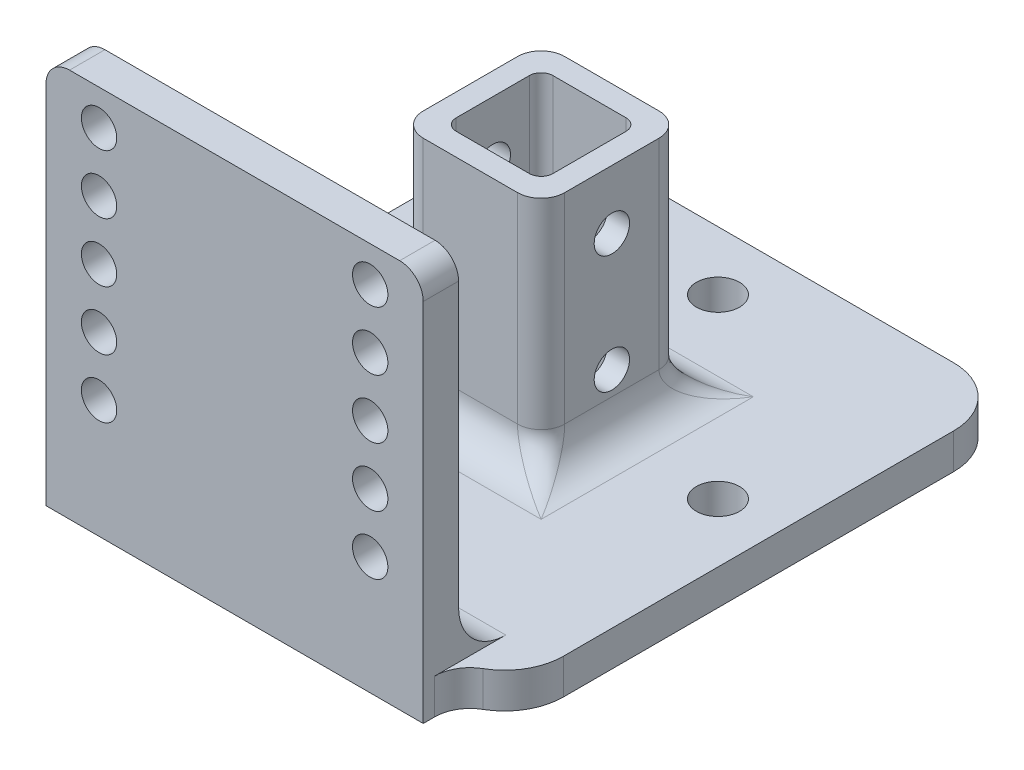
SolidWorks part; units mm, degrees
ref_plane "前视基准面" through (0, 0, 0) normal (0, 0, 1) x (1, 0, 0)
ref_plane "上视基准面" through (0, 0, 0) normal (0, 1, 0) x (1, 0, 0)
ref_plane "右视基准面" through (0, 0, 0) normal (1, 0, 0) x (0, 0, -1)
sketch "草图1" plane through (0, 0, 0) normal (0, 1, 0) x (1, 0, 0)
  line L0 (0, 0) -> (0, 22.885) construction
  line L1 (0, 0) -> (-22.885, 0) construction
  line L3 (-20, -23) -> (20, -23)
  line L4 (-20, -23) -> (-20, 20)
  line L5 (-20, 20) -> (20, 20)
  line L6 (20, -23) -> (20, 20)
  circle A1 centre (0, 15) radius 1.8308
  circle A2 centre (-15, 0) radius 1.8308
  circle A3 centre (0, -15) radius 1.8308
  circle A4 centre (15, 0) radius 1.8308
  dimension "D1" = 15
  dimension "D2" = 15
  dimension "D3" = 43
  dimension "D4" = 40
  dimension "D5" = 20
  dimension "D6" = 23
extrude "凸台-拉伸1" add sketch "草图1" along normal blind 3
sketch "草图3" plane through (0, 0, 23) normal (0, 0, 1) x (1, 0, 0)
  line L0 (-20, 3) -> (20, 3) construction
  line L2 (-16, 3) -> (-16, 33)
  line L3 (-16, 33) -> (16, 33)
  line L4 (16, 3) -> (16, 33)
  line L5 (-20, 3) -> (-20, 0) construction
  line L6 (0, 33) -> (0, 0) construction
  line L7 (-20, 0) -> (20, 0) construction
  line L8 (-16, 0) -> (16, 0)
  line L9 (-16, 0) -> (-16, 3)
  line L11 (16, 0) -> (16, 3)
  circle A0 centre (-11.5, 30) radius 1.5
  circle A1 centre (-11.5, 25) radius 1.5
  circle A2 centre (-11.5, 20) radius 1.5
  circle A3 centre (-11.5, 15) radius 1.5
  circle A4 centre (-11.5, 10) radius 1.5
  circle A6 centre (11.5, 10) radius 1.5
  circle A7 centre (11.5, 15) radius 1.5
  circle A8 centre (11.5, 20) radius 1.5
  circle A9 centre (11.5, 25) radius 1.5
  circle A10 centre (11.5, 30) radius 1.5
  circle A12 centre (-11.5, 5) radius 1.5 [skipped]
  dimension "D4" = 11.5
  dimension "D7" = 3
  dimension "D1" = 30
  dimension "D2" = 32
  dimension "D3" = 4
  dimension "D5" = 6
  dimension "D6" = 3
extrude "凸台-拉伸2" add sketch "草图3" along normal blind 3
fillet "圆角1" radius 2 2 edges at (16, 33, 24.5) (-16, 33, 24.5)
fillet "圆角2" radius 5 4 edges at (-20, 1.5, -20) (-20, 1.5, 23) (20, 1.5, -20) (20, 1.5, 23)
fillet "圆角4" radius 3 2 edges at (16, 1.5, 23) (-16, 1.5, 23)
fillet "圆角3" radius 4 1 edges at (0, 3, 23)
sketch "草图4" plane through (0, 3, 0) normal (0, 1, 0) x (1, 0, 0)
  line L0 (0, 0) -> (-18.5355, 18.5355) construction
  line L1 (0, 0) -> (18.5355, 18.5355) construction
  line L2 (0, 0) -> (0, 20) construction
  line L3 (-20, 0) -> (20.3639, 0) construction
  line L5 (-4.1, -4.1) -> (4.1, -4.1)
  line L6 (-4.1, -4.1) -> (-4.1, 4.1)
  line L7 (-4.1, 4.1) -> (4.1, 4.1)
  line L8 (4.1, -4.1) -> (4.1, 4.1)
  line L9 (-6, -6) -> (6, -6)
  line L10 (-6, -6) -> (-6, 6)
  line L11 (-6, 6) -> (6, 6)
  line L12 (6, -6) -> (6, 6)
  circle A2 centre (0, 0) radius 20 construction
  dimension "D1" = 12
  dimension "D2" = 8.2
  dimension "D3" = 6
  dimension "D4" = 4.1
extrude "凸台-拉伸3" add sketch "草图4" along normal blind 20
sketch "草图5" plane through (0, 0, 0) normal (1, 0, 0) x (0, 0, -1)
  line L3 (0, 0) -> (0, 28.3702) construction
  circle A4 centre (0, 18) radius 1.5
  circle A5 centre (0, 8) radius 1.5
extrude "切除-拉伸1" cut sketch "草图5" against normal through all and the other way through all
fillet "圆角5" radius 3 4 edges at (6, 3, 0) (0, 3, -6) (-6, 3, 0) (0, 3, 6)
fillet "圆角6" radius 2 8 edges at (-6.8787, 3.8787, 6.8787) (-6.8787, 3.8787, -6.8787) (6.8787, 3.8787, -6.8787) (6.8787, 3.8787, 6.8787) (-6, 14.5, 6) (-6, 14.5, -6) (6, 14.5, -6) (6, 14.5, 6)
fillet "圆角7" radius 1 4 edges at (4.1, 13, 4.1) (4.1, 13, -4.1) (-4.1, 13, 4.1) (-4.1, 13, -4.1)
